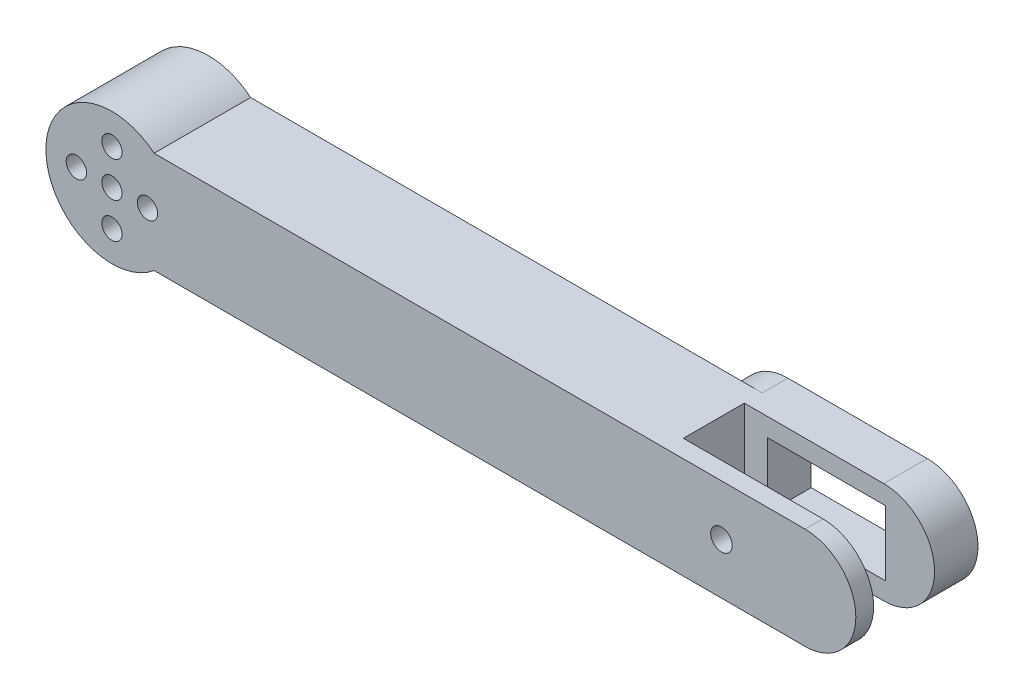
SolidWorks part; units mm, degrees
material "PLA"
ref_plane "Front Plane" through (0, 0, 0) normal (0, 0, 1) x (1, 0, 0)
ref_plane "Top Plane" through (0, 0, 0) normal (0, 1, 0) x (1, 0, 0)
ref_plane "Right Plane" through (0, 0, 0) normal (1, 0, 0) x (0, 0, -1)
sketch "Sketch1" plane through (0, 0, 0) normal (0, 0, 1) x (1, 0, 0)
  circle A0 centre (0, 0) radius 13
  dimension "D1" = 26
extrude "Elbow Boss" add sketch "Sketch1" along normal blind 19
sketch "Sketch2" plane through (0, 0, 0) normal (0, 0, 1) x (1, 0, 0)
  line L0 (0, 0) -> (120, 0) construction
  line L1 (0, 10) -> (120, 10)
  line L2 (0, -10) -> (120, -10)
  arc A0 (0, 10) -> (0, -10) centre (0, 0) ccw
  arc A1 (120, -10) -> (120, 10) centre (120, 0) ccw
  point P3 (60, 0)
  dimension "D1" = 120
  dimension "D2" = 20
extrude "Bar" add sketch "Sketch2" along normal blind 19
sketch "Sketch3" plane through (0, 0, 0) normal (0, 0, -1) x (-1, 0, 0)
  circle A0 centre (0, 0) radius 10.1
  dimension "D1" = 20.2
extrude "Cut-Extrude1" cut sketch "Sketch3" against normal blind 4 and the other way through all
sketch "Sketch4" plane through (0, 0, 4) normal (0, 0, -1) x (-1, 0, 0)
  circle A0 centre (0, 0) radius 4.25
  dimension "D1" = 8.5
extrude "Cut-Extrude2" cut sketch "Sketch4" against normal blind 2.6
sketch "Sketch5" plane through (0, 0, 19) normal (0, 0, 1) x (1, 0, 0)
  circle A0 centre (0, 0) radius 2
  dimension "D1" = 4
extrude "Cut-Extrude3" cut sketch "Sketch5" against normal blind 10
sketch "Sketch6" plane through (0, 0, 19) normal (0, 0, 1) x (1, 0, 0)
  line L0 (0, 0) -> (73.1562, 0) construction
  circle A0 centre (7, 0) radius 2
  dimension "D1" = 4
  dimension "D2" = 7
extrude "Cut-Extrude4" cut sketch "Sketch6" against normal blind 13
sketch "Sketch7" plane through (0, 0, 4) normal (0, 0, -1) x (-1, 0, 0)
  line L0 (0, 0) -> (-49.2438, 0) construction
  circle A0 centre (-7, 0) radius 1.1
  dimension "D2" = 7
  dimension "D1" = 2.2
extrude "Cut-Extrude5" cut sketch "Sketch7" against normal through all
ref_axis "Elbow Axis" through (0, 0, 9) along (0, 0, 1)
pattern_circular "CirPattern1" count 4 over 360 about axis through (0, 0, 9) along (0, 0, 1) of "Cut-Extrude4", "Cut-Extrude5"
ref_axis "Wrist Axis" through (120, 0, 19) along (0, 0, -1)
sketch "Sketch8" plane through (0, 0, 0) normal (0, 0, -1) x (-1, 0, 0)
  line L0 (0, 0) -> (-135.6087, 0) construction
  line L1 (-136.45, 0) -> (-120, 0) construction
  line L2 (-136.45, 10) -> (-120, 10)
  line L3 (-136.45, -10) -> (-120, -10)
  arc A0 (-136.45, 10) -> (-136.45, -10) centre (-136.45, 0) ccw
  arc A1 (-120, -10) -> (-120, 10) centre (-120, 0) ccw
  point P5 (-128.225, 0)
  point P10 (-97.1635, 0)
  point P11 (-91.7429, 0)
  point P12 (-130, 0)
  point P13 (-141.464, 0)
  point P14 (-113.1947, 0)
  point P15 (-135.6087, 0)
  point P16 (-109.8855, 0)
  point P18 (-115.4887, 0)
  point P19 (-130, 0)
  dimension "D1" = 20
  dimension "D2" = 8.225
  dimension "D3" = 16.45
extrude "Boss-Extrude1" add sketch "Sketch8" against normal blind 19
sketch "Sketch9" plane through (0, 0, 0) normal (0, 0, -1) x (-1, 0, 0)
  line L0 (-136.45, 0) -> (-109.03, 0) construction
  line L1 (-136.45, 10) -> (-109.03, 10)
  line L2 (-136.45, -10) -> (-109.03, -10)
  line L3 (0, 0) -> (-183.7235, 0) construction
  arc A0 (-136.45, 10) -> (-136.45, -10) centre (-136.45, 0) ccw
  arc A1 (-109.03, -10) -> (-109.03, 10) centre (-109.03, 0) ccw
  point P2 (-122.74, 0)
  point P10 (0, 0)
  dimension "D2" = 20
  dimension "D1" = 109.03
  dimension "D3" = 136.45
extrude "Boss-Extrude2" add sketch "Sketch9" along normal blind 5.05
ref_plane "Plane1" through (0, 0, 3.5) normal (0, 0, -1) x (-1, 0, 0)
sketch "Sketch10" plane through (0, 0, 3.5) normal (0, 0, -1) x (-1, 0, 0)
  line L0 (0, 0) -> (-171.5743, 0) construction
  line L1 (-169, -20) -> (-109, -20)
  line L2 (-169, -20) -> (-169, 20)
  line L3 (-169, 20) -> (-109, 20)
  line L4 (-109, -20) -> (-109, 20)
  dimension "D1" = 109
  dimension "D2" = 60
  dimension "D3" = 40
extrude "Cut-Extrude6" cut sketch "Sketch10" against normal blind 12
sketch "Sketch11" plane through (0, 0, -5.05) normal (0, 0, -1) x (-1, 0, 0)
  line L0 (-122.74, 10) -> (-122.74, -10) construction
  line L1 (-109.03, 10) -> (-136.45, 10) construction
  line L2 (-136.45, -10) -> (-109.03, -10) construction
  line L3 (0, 0) -> (-164.7935, 0) construction
  circle A0 centre (-111.28, 0) radius 0.85
  circle A2 centre (-139.08, 0) radius 0.85
  point P11 (-143.8037, 0)
  dimension "D1" = 1.7
  dimension "D3" = 27.8
  dimension "D4" = 139.08
  dimension "D2" = 111.28
extrude "Cut-Extrude7" cut sketch "Sketch11" against normal blind 7
sketch "Sketch12" plane through (0, 0, 19) normal (0, 0, 1) x (1, 0, 0)
  circle A0 centre (120, 0) radius 2.125
  point P2 (0, 0)
  dimension "D1" = 4.25
extrude "Cut-Extrude8" cut sketch "Sketch12" against normal up to surface (3.5 mm away) up to face at (125.225, 0, 15.5)
sketch "Sketch13" plane through (0, 0, -5.05) normal (0, 0, -1) x (-1, 0, 0)
  line L0 (-136.75, 6.4) -> (-113.6, -6.4) construction
  line L1 (-113.6, -6.4) -> (-136.75, -6.4)
  line L2 (-113.6, -6.4) -> (-113.6, 6.4)
  line L3 (-113.6, 6.4) -> (-136.75, 6.4)
  line L4 (-136.75, -6.4) -> (-136.75, 6.4)
  line L5 (-113.6, 6.4) -> (-136.75, -6.4) construction
  point P4 (-125.175, 0)
  dimension "D1" = 23.15
  dimension "D2" = 12.8
  dimension "D3" = 125.175
extrude "Cut-Extrude9" cut sketch "Sketch13" against normal up to surface (8.55 mm away) up to face at (125.225, 0, 3.5)
equation "\"L1\"= 120mm'Upper arm"
equation "\"L3\"= 75mm'Wrist→TCP"
equation "\"h0\"= 75mm'Shoulder height"
equation "\"t_link\"= 3mm'Link plate thickness"
equation "\"t_bracket\"= 4mm'Bracket thickness"
equation "\"d_pin\"= 4mm'Pin diameter (M4)"
equation "\"c_fit\"= 0.2mm'Nominal clearance - measured PLA 2026-10-01"
equation "\"L2\"= 120mm'Forearm"
equation "\"c_fit_pivot\"= \"c_fit\" + 0.05mm'Gripper pivot clearance - chosen 0.25 mm 2026-10-01"
equation "\"d_pin_gripper\"= 3mm'Gripper pivot diameter"
equation "\"w_link\"= 20mm'Link plate depth (bending direction)"
equation "\"w_gap\"= 20mm'Twin-plate gap - provisional, set by elbow servo mount"
equation "\"d_boss\"= 13mm'MG996R output boss dia - from downloaded model, verify with calipers"
equation "\"c_boss\"= 1mm'Radial clearance around servo boss"
equation "\"d_servo_hole\"= \"d_boss\" + 2 * \"c_boss\"'Plate clearance hole for servo boss (15 mm)"
equation "\"t_rim\"= 9.5mm'Min material around servo hole (M3 hole + 3 mm webs each side)"
equation "\"w_link_end\"= \"d_servo_hole\" + 2 * \"t_rim\"'Link plate end width at servo end (34 mm)"
equation "\"d_hole_m3\"= \"d_pin_gripper\" + \"c_fit\"'M3 bolt clearance hole (spacer and adapter bolts)"
equation "\"d_hole_pivot\"= \"d_pin\" + \"c_fit_pivot\"'M4 pivot hole where the pin rotates (4.25 mm)"
equation "\"d_horn\"= 20mm'Horn disc diameter (circular horn) - from MG996R model"
equation "\"t_horn\"= 2.3mm'Horn disc thickness"
equation "\"g_horn\"= 2.2mm'Gap from horn disc to plate 2 inner face - from MockShoulder"
equation "\"d_horn_pocket\"= \"d_horn\" + \"c_fit\"'Adapter pocket for horn disc (20.2 mm)"
equation "\"h_horn_pocket\"= \"g_horn\" + \"t_horn\"'Pocket depth from adapter plate-2 face (4.5 mm)"
equation "\"d_horn_screw_cb\"= 8.5mm'Recess for horn centre-screw head (head is 7.5 mm)"
equation "\"h_horn_screw_cb\"= 2.6mm'Recess depth (head is 2.35 mm tall)"
equation "\"d_adapter\"= 26mm'Horn adapter outer diameter"
equation "\"h_adapter\"= \"w_gap\"'Adapter length, fills the plate gap"
equation "\"t_adapter_floor\"= 2mm'Floor under horn disc that the horn screws pass through"
equation "\"d_horn_screw_hole\"= 2.2mm'Clearance for M2 self-tapper through the floor"
equation "\"r_horn_screw\"= 7mm'Horn screw hole radius (14 mm square pattern)"
equation "\"d_access\"= 4mm'Access bore for the M2 screws from the plate-1 side"
equation "\"d_insert_m3\"= 4mm'Hole for M3 heat-set insert - HZYUEGOU M3 inserts are 4.2 OD, hole 4.0; open to 4.1 if too tight"
equation "\"h_insert_m3\"= 6mm'Insert hole depth"
equation "\"x_adapter_bolt\"= 6mm'Adapter bolt offset from pin, along the arm toward its middle"
equation "\"y_adapter_bolt\"= 5mm'Adapter bolt offset from pin, across the arm (+/-)"
equation "\"d_csk_m3\"= 6.4mm'Countersink diameter in plate 1 for M3 flat head (90 deg)"
equation "\"h_pin_bore\"= 10mm'M4 pin engagement depth in the adapter"
equation "\"c_win\"= 0.3mm'Servo window clearance per side in bracket wall A - starting value, tune after a test print"
equation "\"l_servo\"= 40.9mm'MG996R case length without ears - from the model"
equation "\"w_servo\"= 20mm'MG996R case width - from the model"
equation "\"r_servo_short\"= 10mm'Shaft axis to the short end of the case - from the model"
equation "\"r_servo_long\"= \"l_servo\" - \"r_servo_short\"'Shaft axis to the long end of the case (30.9 mm)"
equation "\"l_ear_holes\"= 48.6mm'MG996R ear hole (keyhole slot) spacing along the case - from the model"
equation "\"w_ear_holes\"= 10mm'MG996R ear hole spacing across the case - from the model"
equation "\"a_ear\"= 8.2mm'Servo ear seating face to plate-2 outer face - from MockShoulder (ear face incl. 0.2 edge round)"
equation "\"l_window\"= \"l_servo\" + 2 * \"c_win\"'Wall A window length (41.5 mm)"
equation "\"w_window\"= \"w_servo\" + 2 * \"c_win\"'Wall A window width (20.6 mm)"
equation "\"g_wall_a\"= \"a_ear\" - \"t_bracket\"'Gap behind wall A to plate 2 (4.2 mm) - ear screw heads sit here"
equation "\"g_wall_b\"= 1mm'Plate 1 outer face to wall B - thrust washer"
equation "\"d_axis_turret\"= 34mm'Shoulder axis to turret mounting face - PLACEHOLDER until the turret is designed"
equation "\"t_foot\"= 6mm'Bracket foot thickness"
equation "\"h_wall_top\"= 41.5mm'Wall A top above the shoulder axis (long-end ear holes + 4 mm)"
equation "\"w_wall\"= 30mm'Bracket wall A and B width"
equation "\"w_foot\"= 50mm'Bracket foot width across the walls"
equation "\"t_boss_b\"= 4mm'Extra thickness of the pin boss on the outside of wall B"
equation "\"d_boss_b\"= 12mm'Pin boss diameter on wall B"
equation "\"r_wall_corner\"= 10mm'Wall A top corner radius"
equation "\"l_notch\"= 6.4mm'Ear rib notch length past each end of the wall A window - from the model"
equation "\"w_notch\"= 1.66mm'Ear rib notch width (1.0 rib + 0.33 each side)"
equation "\"l_foot_back\"= 11.6mm'Bracket foot overhang behind wall A outer face"
equation "\"l_foot_front\"= 11mm'Bracket foot overhang past wall B outer face"
equation "\"w_turret_holes\"= 40mm'Turret bolt pattern across the foot (X)"
equation "\"e_turret_hole\"= 4.8mm'Foot insert hole centre to foot end (2.8 mm plastic with d_insert_m3 = 4.0)"
equation "\"z_wall_b_out\"= \"a_ear\" + 2 * \"t_link\" + \"w_gap\" + \"g_wall_b\" + \"t_bracket\"'Wall B outer face from wall A outer face (39.2 mm)"
equation "\"z_turret_hole\"= \"z_wall_b_out\" + \"l_foot_front\" - \"e_turret_hole\"'Upper foot insert holes from wall A outer face (45.4 mm); lower pair mirrors about the foot centre"
equation "\"r_foot_fillet\"= 4mm'Wall-to-foot fillet radius"
equation "\"c_side\"= 0.5mm'Forearm running clearance to each upper-arm plate at the elbow"
equation "\"w_forearm\"= \"w_gap\" - 2 * \"c_side\"'Solid forearm width along the elbow axis (19 mm)"
equation "\"h_forearm\"= \"w_link\"'Forearm depth in the arm plane (20 mm, same as the plates)"
equation "\"h_horn_pocket_fa\"= \"g_horn\" - \"c_side\" + \"t_horn\"'Elbow horn pocket depth from the forearm plate-1 face (4.0 mm)"
equation "\"h_dowel_fa\"= 10mm'Elbow dowel depth in the forearm - press fit, hole = d_pin"
equation "\"l_dowel_elbow\"= \"h_dowel_fa\" + \"c_side\" + \"t_link\"'Elbow dowel length, flush with plate 2 outer face (13.5 mm)"
equation "\"r_mount_bolt\"= \"L1\" / 4'Elbow axis to the upper-arm spacer holes on the shoulder side (30 mm) - elbow servo mount bolts through these"
equation "\"h_standoff\"= \"g_wall_a\"'Elbow mount standoffs, wall to plate 1 outer face (4.2 mm)"
equation "\"d_standoff\"= 7mm'Elbow mount standoff diameter, same as the upper-arm spacers"
equation "\"e_mount\"= 5mm'Elbow mount wall end past the standoff hole centres (3.4 mm plastic outside the hole)"
equation "\"l_mount_back\"= \"r_mount_bolt\" + \"e_mount\"'Elbow mount wall end toward the shoulder, from the elbow axis (35 mm)"
equation "\"l_mount_bolt\"= \"t_bracket\" + \"h_standoff\" + 2 * \"t_link\" + \"w_gap\"'Grip of the two spacer bolts through the elbow mount (34.2 mm) - M3x40 + nut"
equation "\"D1@Sketch1\"=\"d_adapter\""
equation "\"D1@Elbow Boss\" = \"w_forearm\""
equation "\"D1@Sketch2\"=\"L2\""
equation "\"D2@Sketch2\"=\"h_forearm\""
equation "\"D1@Bar\" = \"w_forearm\""
equation "\"D1@Sketch3\"=\"d_horn_pocket\""
equation "\"D1@Cut-Extrude1\"=\"h_horn_pocket_fa\""
equation "\"D1@Sketch4\"=\"d_horn_screw_cb\""
equation "\"D1@Cut-Extrude2\"=\"h_horn_screw_cb\""
equation "\"D1@Sketch5\"=\"d_pin\""
equation "\"D1@Cut-Extrude3\"=\"h_dowel_fa\""
equation "\"D1@Sketch6\"=\"d_access\""
equation "\"D2@Sketch6\"=\"r_horn_screw\""
equation "\"D1@Cut-Extrude4\"=\"w_forearm\"-\"h_horn_pocket_fa\"-\"t_adapter_floor\""
equation "\"D1@Sketch7\"=\"d_horn_screw_hole\""
equation "\"D2@Sketch7\"=\"r_horn_screw\""
equation "\"l_sg90\"= 22.55mm'SG90 case length without ears - DF9GMS 2026-10-24, chosen by Haseeb (calipered 22.65-22.85; model 22.5)"
equation "\"w_sg90\"= 12.2mm'SG90 case width - kept at the model value by Haseeb 2026-10-24 (calipered 11.92)"
equation "\"t_sg90_ear\"= 2.5mm'SG90 ear thickness - calipered DF9GMS 2026-10-24, matches model"
equation "\"l_sg90_ears\"= 32.29mm'SG90 ear tip to tip - calipered DF9GMS 2026-10-24 (model 32.1)"
equation "\"l_sg90_ear_holes\"= 27.8mm'SG90 ear hole spacing, centre to centre - calipered DF9GMS 2026-10-24, matches model"
equation "\"r_sg90_shaft\"= 6.1mm'SG90 shaft axis to the case end face the cable leaves from - calipered DF9GMS 2026-10-24, matches model"
equation "\"h_sg90_tower\"= 8.55mm'SG90 top of the raised gear housing above the top face of the ears - calipered DF9GMS 2026-10-24, matches model"
equation "\"h_sg90_spline\"= 3.1mm'SG90 spline height above the raised gear housing - GrabCAD model"
equation "\"d_pilot_m2\"= 1.7mm'Pilot hole for M2 self-tappers into PLA (SG90 ear screws) - chosen, test on a print"
equation "\"h_pilot_m2\"= 7mm'Pilot hole depth for the SG90 ear screws"
equation "\"l_sg90_window\"= \"l_sg90\" + 2 * \"c_win\"'SG90 window through the servo-side prong (23.15 mm)"
equation "\"w_sg90_window\"= \"w_sg90\" + 2 * \"c_win\"'SG90 window width (12.8 mm)"
equation "\"x_sg90_centre\"= \"l_sg90\" / 2 - \"r_sg90_shaft\"'SG90 case centre past the wrist axis, toward the forearm tip (5.175 mm) - cable end toward the elbow"
equation "\"l_wrist_ext\"= \"l_sg90\" - \"r_sg90_shaft\"'Forearm round-end centre past the wrist axis = far end of the SG90 case (16.45 mm)"
equation "\"g_clevis\"= 12mm'Wrist clevis gap, centred on the forearm mid-plane"
equation "\"t_prong\"= ( \"w_forearm\" - \"g_clevis\" ) / 2'Clevis prong thickness before the flare (3.5 mm) - the pin-side prong stays this"
equation "\"t_flare\"= \"h_sg90_tower\" - \"t_prong\"'Wrist flare on the Z = 0 side (5.05 mm) - SG90 ears seat on it, gear housing ends flush with the gap; servo-side prong 8.55"
equation "\"x_flare\"= \"L2\" + \"x_sg90_centre\" - \"l_sg90_ears\" / 2'Flare slot first centre, at the elbow-side SG90 ear tip (109.03 mm)"
equation "\"x_clevis\"= \"L2\" - \"h_forearm\" / 2 - 1mm'Clevis gap closed end, 1 mm behind the R10 end of the wrist piece (109 mm)"
equation "\"D1@Sketch8\"=\"h_forearm\""
equation "\"D3@Sketch8\"=\"l_wrist_ext\""
equation "\"D1@Boss-Extrude1\"=\"w_forearm\""
equation "\"D1@Sketch9\"=\"x_flare\""
equation "\"D2@Sketch9\"=\"h_forearm\""
equation "\"D1@Boss-Extrude2\"=\"t_flare\""
equation "\"D1@Sketch10\"=\"x_clevis\""
equation "\"D1@Sketch12\"=\"d_hole_pivot\""
equation "\"D1@Sketch13\"=\"l_sg90_window\""
equation "\"D2@Sketch13\"=\"w_sg90_window\""
equation "\"D3@Sketch13\"=\"L2\" + \"x_sg90_centre\""
